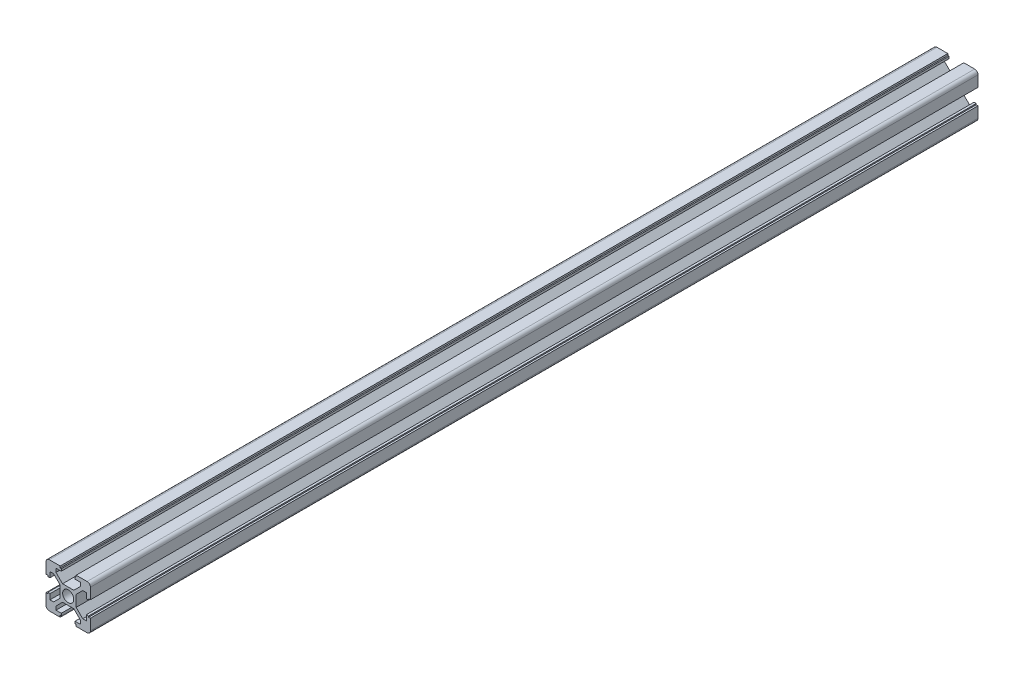
SolidWorks part; units mm, degrees
ref_plane "前视基准面" through (0, 0, 0) normal (0, 0, 1) x (1, 0, 0)
ref_plane "上视基准面" through (0, 0, 0) normal (0, 1, 0) x (1, 0, 0)
ref_plane "右视基准面" through (0, 0, 0) normal (1, 0, 0) x (0, 0, -1)
other "Configuration Table"
sketch "草图1" plane through (0, 0, 0) normal (0, 0, 1) x (1, 0, 0)
  line L0 (-4.4156, 1.3346) -> (-4.4156, 4.4346) construction
  line L1 (-4.4156, 3.874) -> (-4.4156, -1.2047)
  line L2 (1.7237, 4.9346) -> (-3.3549, 4.9346)
  line L3 (2.7844, -1.2047) -> (2.7844, 3.874)
  line L4 (-3.3549, -2.2654) -> (1.7237, -2.2654)
  line L5 (-10.8156, 1.3346) -> (9.1844, 1.3346) construction
  line L6 (-0.8156, 11.3346) -> (-0.8156, -8.6654) construction
  line L7 (-10.8156, 11.3346) -> (-0.8156, 1.3346) construction
  line L8 (-10.8156, 4.9346) -> (-4.4156, 4.9346) construction
  line L9 (-10.0156, 4.4346) -> (-3.9156, 4.4346) construction
  line L10 (-9.0156, 6.8346) -> (-6.3156, 6.8346) construction
  line L11 (-7.3763, 6.8346) -> (-4.4156, 3.874) construction
  line L12 (-10.8156, 9.8346) -> (-10.8156, 4.9346)
  line L13 (-10.8156, 4.9346) -> (-10.0156, 4.9346)
  line L14 (-10.0156, 4.9346) -> (-10.0156, 4.4346)
  line L15 (-10.0156, 4.4346) -> (-9.0156, 4.4346)
  line L16 (-9.0156, 4.4346) -> (-9.0156, 6.8346)
  line L17 (-9.0156, 6.8346) -> (-7.3763, 6.8346)
  line L18 (-7.3763, 6.8346) -> (-4.4156, 3.874)
  line L19 (-3.9156, 10.5346) -> (-3.9156, 9.5346)
  line L20 (-4.4156, 10.5346) -> (-3.9156, 10.5346)
  line L21 (-4.4156, 11.3346) -> (-4.4156, 10.5346)
  line L22 (-9.3156, 11.3346) -> (-4.4156, 11.3346)
  line L23 (-3.9156, 9.5346) -> (-6.3156, 9.5346)
  line L24 (-6.3156, 9.5346) -> (-6.3156, 7.8953)
  line L25 (-6.3156, 7.8953) -> (-3.3549, 4.9346)
  line L26 (9.1844, 11.3346) -> (-0.8156, 1.3346) construction
  line L27 (4.6844, 7.8953) -> (1.7237, 4.9346)
  line L28 (4.6844, 9.5346) -> (4.6844, 7.8953)
  line L29 (2.2844, 9.5346) -> (4.6844, 9.5346)
  line L30 (2.2844, 10.5346) -> (2.2844, 9.5346)
  line L31 (2.7844, 10.5346) -> (2.2844, 10.5346)
  line L32 (2.7844, 11.3346) -> (2.7844, 10.5346)
  line L33 (7.6844, 11.3346) -> (2.7844, 11.3346)
  line L34 (9.1844, 9.8346) -> (9.1844, 4.9346)
  line L35 (9.1844, 4.9346) -> (8.3844, 4.9346)
  line L36 (8.3844, 4.9346) -> (8.3844, 4.4346)
  line L37 (8.3844, 4.4346) -> (7.3844, 4.4346)
  line L38 (7.3844, 4.4346) -> (7.3844, 6.8346)
  line L39 (7.3844, 6.8346) -> (5.7451, 6.8346)
  line L40 (5.7451, 6.8346) -> (2.7844, 3.874)
  line L41 (9.1844, -8.6654) -> (-0.8156, 1.3346) construction
  line L42 (5.7451, -4.1654) -> (2.7844, -1.2047)
  line L43 (7.3844, -4.1654) -> (5.7451, -4.1654)
  line L44 (7.3844, -1.7654) -> (7.3844, -4.1654)
  line L45 (8.3844, -1.7654) -> (7.3844, -1.7654)
  line L46 (8.3844, -2.2654) -> (8.3844, -1.7654)
  line L47 (9.1844, -2.2654) -> (8.3844, -2.2654)
  line L48 (9.1844, -7.1654) -> (9.1844, -2.2654)
  line L49 (7.6844, -8.6654) -> (2.7844, -8.6654)
  line L50 (2.7844, -8.6654) -> (2.7844, -7.8654)
  line L51 (2.7844, -7.8654) -> (2.2844, -7.8654)
  line L52 (2.2844, -7.8654) -> (2.2844, -6.8654)
  line L53 (2.2844, -6.8654) -> (4.6844, -6.8654)
  line L54 (4.6844, -6.8654) -> (4.6844, -5.226)
  line L55 (4.6844, -5.226) -> (1.7237, -2.2654)
  line L56 (-10.8156, -8.6654) -> (-0.8156, 1.3346) construction
  line L57 (-6.3156, -5.226) -> (-3.3549, -2.2654)
  line L58 (-6.3156, -6.8654) -> (-6.3156, -5.226)
  line L59 (-3.9156, -6.8654) -> (-6.3156, -6.8654)
  line L60 (-3.9156, -7.8654) -> (-3.9156, -6.8654)
  line L61 (-4.4156, -7.8654) -> (-3.9156, -7.8654)
  line L62 (-4.4156, -8.6654) -> (-4.4156, -7.8654)
  line L63 (-9.3156, -8.6654) -> (-4.4156, -8.6654)
  line L64 (-10.8156, -7.1654) -> (-10.8156, -2.2654)
  line L65 (-10.8156, -2.2654) -> (-10.0156, -2.2654)
  line L66 (-10.0156, -2.2654) -> (-10.0156, -1.7654)
  line L67 (-10.0156, -1.7654) -> (-9.0156, -1.7654)
  line L68 (-9.0156, -1.7654) -> (-9.0156, -4.1654)
  line L69 (-9.0156, -4.1654) -> (-7.3763, -4.1654)
  line L70 (-7.3763, -4.1654) -> (-4.4156, -1.2047)
  arc A0 (-10.8156, 9.8346) -> (-9.3156, 11.3346) centre (-9.3156, 9.8346) cw
  circle A1 centre (-0.8156, 1.3346) radius 2.5
  arc A2 (7.6844, 11.3346) -> (9.1844, 9.8346) centre (7.6844, 9.8346) cw
  arc A3 (9.1844, -7.1654) -> (7.6844, -8.6654) centre (7.6844, -7.1654) cw
  arc A4 (-9.3156, -8.6654) -> (-10.8156, -7.1654) centre (-9.3156, -7.1654) cw
  point P13 (-0.8156, 1.3346)
  point P84 (-0.8156, 1.3346)
  dimension "D8" = 1.5
  dimension "D9" = 5
  dimension "D1" = 20
  dimension "D2" = 6.2
  dimension "D3" = 7.2
  dimension "D4" = 11
  dimension "D5" = 1.5
  dimension "D6" = 0.8
  dimension "D7" = 1.8
  dimension "D10" = 7.2
extrude "凸台-拉伸1" add sketch "草图1" along normal blind 400 contours A1 | L34 L35 L36 L37 L38 L39 L40 L3 L42 L43 L44 L45 L46 L47 L48 A3 L49 L50 L51 L52 L53 L54 L55 L4 L57 L58 L59 L60 L61 L62 L63 A4 L64 L65 L66 L67 L68 L69 L70 L1 L18 L17 L16 L15 L14 L13 L12 A0 L22 L21 L20 L19 L23 L24 L25 L2 L27 L28 L29 L30 L31 L32 L33 A2 region at (-0.8156, 1.3346, 0)
sketch "草图2" plane through (-4.4156, 0, 0) normal (-1, 0, 0) x (0, 0, 1)
  circle A0 centre (320, 1.3346) radius 1.75
  circle A2 centre (80, 1.3346) radius 1.75
extrude "切除-拉伸2" cut sketch "草图2" against normal blind 21 contours A0 | A2 region at (-4.4156, 1.3346, 320)
